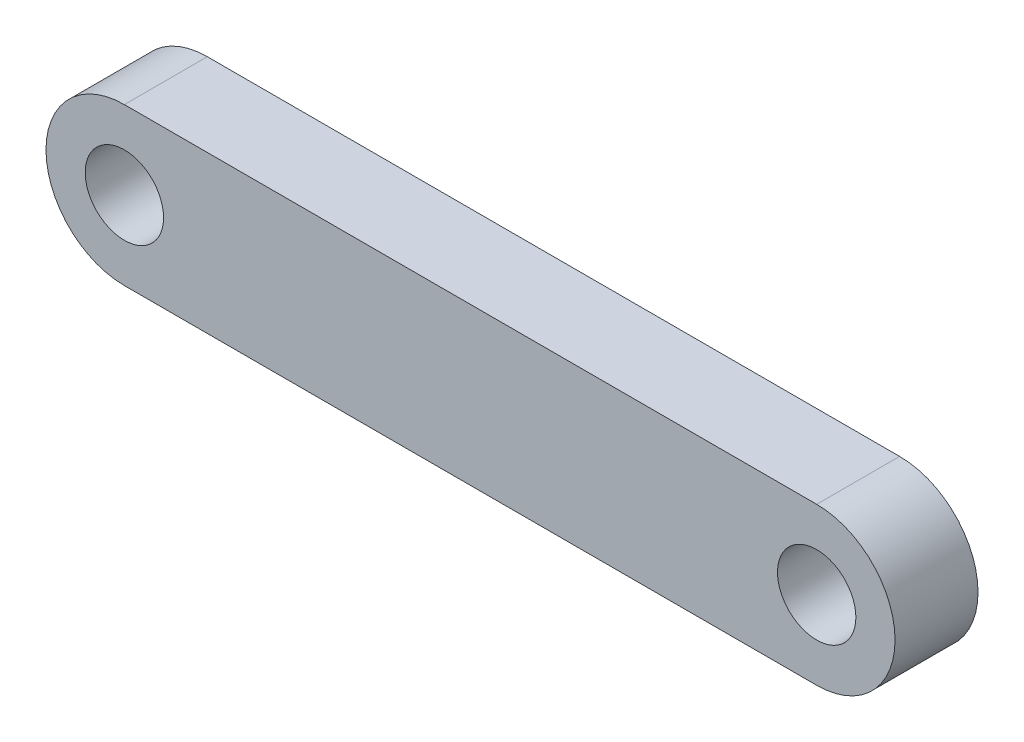
SolidWorks part; units mm, degrees
material "Cast Carbon Steel"
ref_plane "Front Plane" through (0, 0, 0) normal (0, 0, 1) x (1, 0, 0)
ref_plane "Top Plane" through (0, 0, 0) normal (0, 1, 0) x (1, 0, 0)
ref_plane "Right Plane" through (0, 0, 0) normal (1, 0, 0) x (0, 0, -1)
sketch "Sketch1" plane through (0, 0, 0) normal (0, 0, 1) x (1, 0, 0)
  line L0 (-53, 0) -> (53, 0) construction
  line L1 (-53, 12) -> (53, 12)
  line L2 (-53, -12) -> (53, -12)
  circle A0 centre (-53, 0) radius 6
  circle A1 centre (53, 0) radius 6
  arc A2 (-53, 12) -> (-53, -12) centre (-53, 0) ccw
  arc A3 (53, -12) -> (53, 12) centre (53, 0) ccw
  point P4 (0, 0)
  dimension "D2" = 12
  dimension "D3" = 24
  dimension "D4" = 24
  dimension "D1" = 106
extrude "Boss-Extrude1" add sketch "Sketch1" along normal blind 12.7
